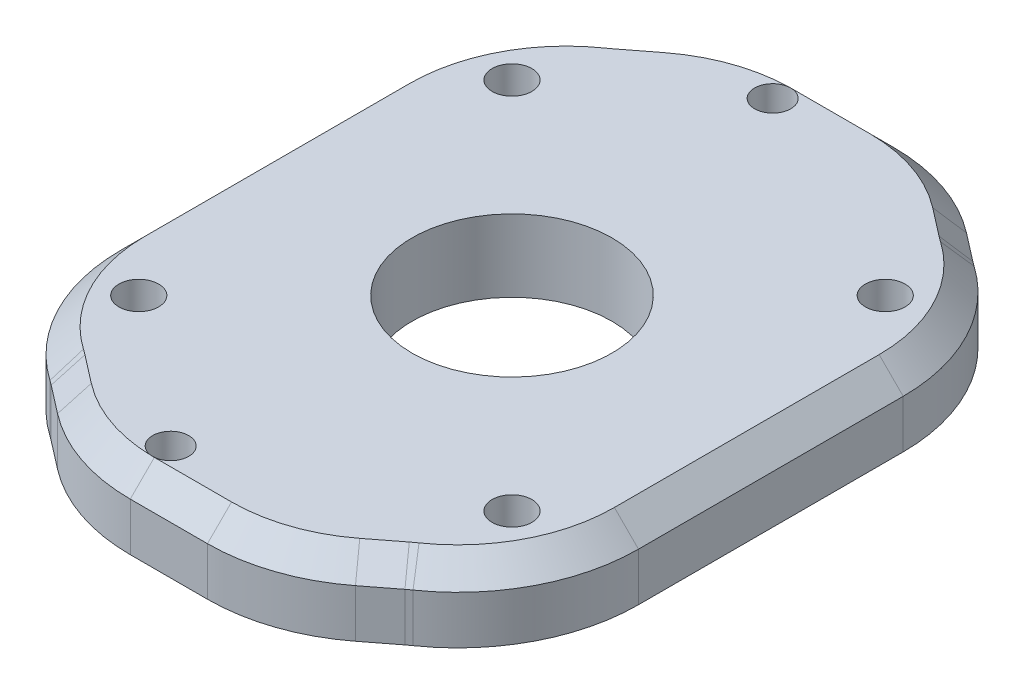
SolidWorks part; units mm, degrees
material "ABS"
ref_plane "Płaszczyzna przednia" through (0, 0, 0) normal (0, 0, 1) x (1, 0, 0)
ref_plane "Płaszczyzna górna" through (0, 0, 0) normal (0, 1, 0) x (1, 0, 0)
ref_plane "Płaszczyzna prawa" through (0, 0, 0) normal (1, 0, 0) x (0, 0, -1)
sketch "Szkic1" plane through (0, 0, 0) normal (0, 1, 0) x (1, 0, 0)
  line L4 (-25.9035, -8.4933) -> (-19.4915, -8.4933)
  line L5 (-10.3266, -5.3678) -> (-8.0064, -3.577)
  line L6 (-1.1975, 9.0122) -> (-1.1975, 31.0012)
  line L7 (-8.0064, 43.5904) -> (-10.3266, 45.3812)
  line L8 (-19.4915, 48.5067) -> (-25.9035, 48.5067)
  line L10 (-22.6975, 20.0067) -> (-22.6975, 48.5067) construction
  line L11 (-37.3887, 43.5904) -> (-35.0685, 45.3812)
  line L12 (-44.1975, 9.0122) -> (-44.1975, 31.0012)
  line L13 (-35.0685, -5.3678) -> (-37.3887, -3.577)
  circle A0 centre (-22.6975, 20.0067) radius 8
  circle A1 centre (-38.1975, 35.5067) radius 1.65
  circle A2 centre (-26.0475, 45.0067) radius 1.5
  circle A3 centre (-7.1975, 35.5067) radius 1.65
  circle A4 centre (-38.1975, 4.5067) radius 1.65
  circle A5 centre (-26.0475, -4.9933) radius 1.5
  circle A6 centre (-7.1975, 4.5067) radius 1.65
  circle A7 centre (-22.6975, 20.0067) radius 8.3
  arc A14 (-19.4915, -8.4933) -> (-10.3266, -5.3678) centre (-19.4915, 6.5067) ccw
  arc A15 (-7.6168, -3.2911) -> (-8.0064, -3.577) centre (-1.8964, -11.4933) ccw
  arc A16 (-7.6168, -3.2911) -> (-1.1975, 9.0122) centre (-16.1975, 9.0122) ccw
  arc A17 (-1.1975, 31.0012) -> (-7.6168, 43.3045) centre (-16.1975, 31.0012) ccw
  arc A18 (-8.0064, 43.5904) -> (-7.6168, 43.3045) centre (-1.8964, 51.5067) ccw
  arc A19 (-10.3266, 45.3812) -> (-19.4915, 48.5067) centre (-19.4915, 33.5067) ccw
  arc A23 (-35.0685, 45.3812) -> (-25.9035, 48.5067) centre (-25.9035, 33.5067) cw
  arc A24 (-37.3887, 43.5904) -> (-37.7782, 43.3045) centre (-43.4987, 51.5067) cw
  arc A25 (-44.1975, 31.0012) -> (-37.7782, 43.3045) centre (-29.1975, 31.0012) cw
  arc A26 (-37.7782, -3.2911) -> (-44.1975, 9.0122) centre (-29.1975, 9.0122) cw
  arc A27 (-37.7782, -3.2911) -> (-37.3887, -3.577) centre (-43.4987, -11.4933) cw
  arc A28 (-25.9035, -8.4933) -> (-35.0685, -5.3678) centre (-25.9035, 6.5067) cw
  dimension "D1" = 0.3
extrude "Dodanie-wyciągnięcie1" add sketch "Szkic1" along normal blind 6 contours A7 L8 A23 L11 A24 A25 L12 A26 A27 L13 A28 L4 A14 L5 A15 A16 L6 A17 A18 L7 A19 A6 A5 A4 A3 A2 A1 region at (-30.5147, 0, 7.0146)
chamfer "Sfazowanie1" distance 2 angle 45 20 edges at (-1.1975, 6, -20.0067) (-2.8988, 6, -2.0736) (-2.8988, 6, -37.9398) (-7.8133, 6, 3.4317) (-7.8133, 6, -43.4451) (-9.1665, 6, 4.4724) (-9.1665, 6, -44.4858) (-14.6499, 6, 7.6904) (-14.6499, 6, -47.7039) (-22.6975, 6, 8.4933) (-22.6975, 6, -48.5067) (-30.7452, 6, 7.6904) (-30.7452, 6, -47.7039) (-36.2286, 6, 4.4724) (-36.2286, 6, -44.4858) (-37.5817, 6, 3.4317) (-37.5817, 6, -43.4451) (-42.4962, 6, -2.0736) (-42.4962, 6, -37.9398) (-44.1975, 6, -20.0067)
sketch "Szkic2" plane through (0, 0, 0) normal (0, -1, 0) x (1, 0, 0)
  circle A0 centre (-38.1975, -35.5067) radius 1.65 construction
  circle A1 centre (-26.0475, -45.0067) radius 1.5 construction
  circle A2 centre (-7.1975, -35.5067) radius 1.65 construction
  circle A3 centre (-7.1975, -4.5067) radius 1.65 construction
  circle A4 centre (-38.1975, -4.5067) radius 1.65 construction
  circle A5 centre (-26.0475, 4.9933) radius 1.5 construction
  circle A6 centre (-38.1975, -35.5067) radius 1.65
  circle A7 centre (-26.0475, -45.0067) radius 1.5
  circle A8 centre (-7.1975, -35.5067) radius 1.65
  circle A9 centre (-7.1975, -4.5067) radius 1.65
  circle A10 centre (-38.1975, -4.5067) radius 1.65
  circle A11 centre (-26.0475, 4.9933) radius 1.5
extrude "Dodanie-wyciągnięcie2" add sketch "Szkic2" against normal blind 0.2
